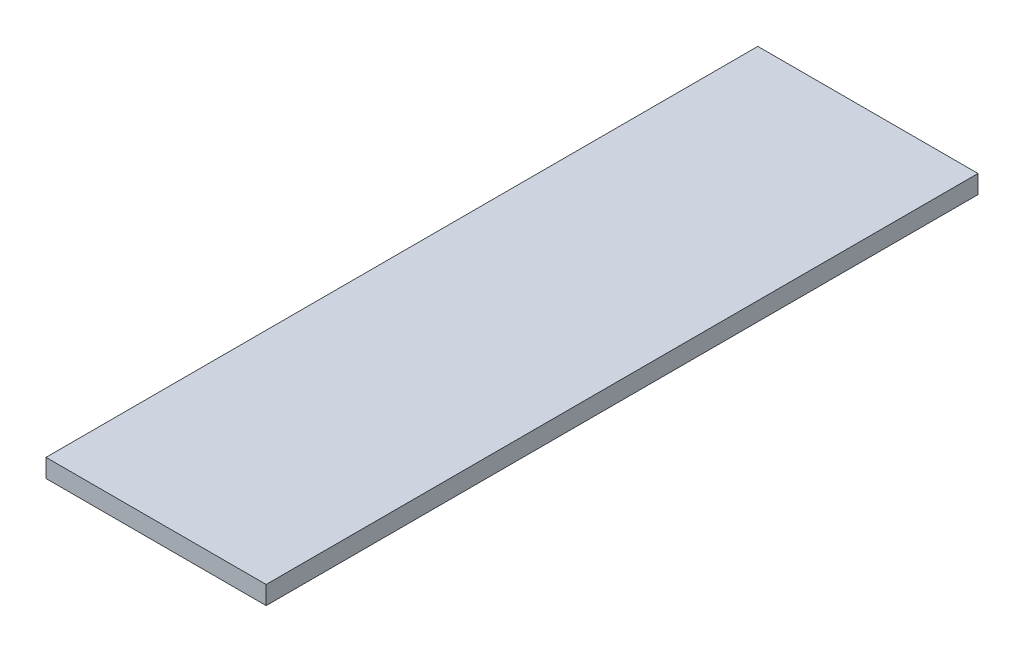
SolidWorks part; units mm, degrees
ref_plane "Front Plane" through (0, 0, 0) normal (0, 0, 1) x (1, 0, 0)
ref_plane "Top Plane" through (0, 0, 0) normal (0, 1, 0) x (1, 0, 0)
ref_plane "Right Plane" through (0, 0, 0) normal (1, 0, 0) x (0, 0, -1)
sketch "Sketch1" plane through (0, 0, 0) normal (0, 1, 0) x (1, 0, 0)
  line L1 (0, 0) -> (60, 0)
  line L3 (0, -194) -> (60, -194)
  line L5 (0, 0) -> (0, -194)
  line L9 (60, 0) -> (60, -194)
  dimension "D1" = 194
  dimension "D2" = 60
extrude "Boss-Extrude1" add sketch "Sketch1" along normal blind 5
